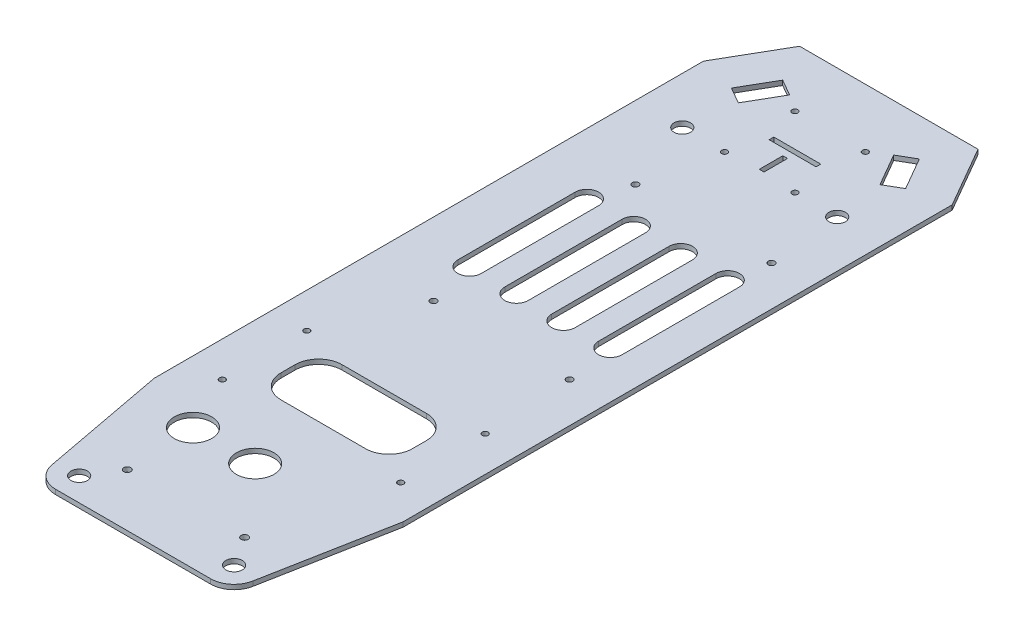
SolidWorks part; units mm, degrees
material "Epoxy, renforcé"
ref_plane "Plan de face" through (0, 0, 0) normal (0, 0, 1) x (1, 0, 0)
ref_plane "Plan de dessus" through (0, 0, 0) normal (0, 1, 0) x (1, 0, 0)
ref_plane "Plan de droite" through (0, 0, 0) normal (1, 0, 0) x (0, 0, -1)
sketch "Esquisse1" plane through (0, 0, 0) normal (0, 1, 0) x (1, 0, 0)
  line L0 (-33, 128.5) -> (33, 128.5) construction
  line L1 (33, 128.5) -> (33, -128.5) construction
  line L2 (33, -128.5) -> (-33, -128.5) construction
  line L3 (-33, -128.5) -> (-33, 128.5) construction
  line L4 (0, 128.5) -> (0, 0) construction
  line L5 (33, 0) -> (0, 0) construction
  line L6 (53, 183.5) -> (-53, 183.5)
  line L7 (-53, 183.5) -> (-53, -148.5)
  line L8 (-53, -148.5) -> (53, -148.5)
  line L9 (53, 183.5) -> (53, -148.5)
  circle A0 centre (-33, 128.5) radius 3.5
  circle A1 centre (-33, -128.5) radius 3.5
  circle A2 centre (33, 128.5) radius 3.5
  circle A3 centre (33, -128.5) radius 3.5
  point P17 (0, -148.5)
  point P18 (0, 183.5)
  dimension "D1" = 7
  dimension "D2" = 7
  dimension "D3" = 7
  dimension "D4" = 7
  dimension "D5" = 66
  dimension "D6" = 257
  dimension "D7" = 55
  dimension "D8" = 20
  dimension "D9" = 20
extrude "Boss.-Extru.1" add sketch "Esquisse1" along normal blind 2
sketch "Esquisse3" plane through (0, 2, 0) normal (0, 1, 0) x (1, 0, 0)
  line L0 (-22, 11.5) -> (-22, 97.5) construction
  line L1 (-22, 97.5) -> (36, 97.5) construction
  line L2 (36, 97.5) -> (36, 11.5) construction
  line L3 (36, 11.5) -> (-22, 11.5) construction
  line L4 (53, -148.5) -> (53, 183.5) construction
  line L5 (53, 183.5) -> (-53, 183.5) construction
  circle A4 centre (-22, 11.5) radius 1.375
  circle A5 centre (-22, 97.5) radius 1.375
  circle A6 centre (36, 97.5) radius 1.375
  circle A7 centre (36, 11.5) radius 1.375
  dimension "D1" = 86
  dimension "D2" = 58
  dimension "D3" = 17
  dimension "D4" = 86
extrude "Enlèv. mat.-Extru.1" cut sketch "Esquisse3" against normal through all
chamfer "Chanfrein1" distance 15 angle 60 2 edges at (-53, 1, -183.5) (53, 1, -183.5) first distance on face at (0, 1, -183.5)
sketch "Esquisse4" plane through (0, 2, 0) normal (0, 1, 0) x (1, 0, 0)
  line L0 (0, -62.5) -> (0, -148.5) construction
  line L1 (38, -62.5) -> (-38, -62.5) construction
  line L2 (38, -62.5) -> (38, -26.5) construction
  line L3 (38, -26.5) -> (-38, -26.5) construction
  line L4 (-38, -62.5) -> (-38, -26.5) construction
  line L5 (-53, -148.5) -> (53, -148.5) construction
  line L6 (38, 183.5) -> (-38, 183.5) construction
  line L7 (-28, -57.5) -> (28, -57.5)
  line L8 (-28, -57.5) -> (-28, -31.5)
  line L9 (-28, -31.5) -> (28, -31.5)
  line L10 (28, -57.5) -> (28, -31.5)
  circle A0 centre (38, -62.5) radius 1.25
  circle A1 centre (38, -26.5) radius 1.25
  circle A2 centre (-38, -62.5) radius 1.25
  circle A3 centre (-38, -26.5) radius 1.25
  dimension "D3" = 2.5
  dimension "D4" = 2.5
  dimension "D5" = 2.5
  dimension "D6" = 2.5
  dimension "D1" = 76
  dimension "D2" = 36
  dimension "D7" = 210
  dimension "D8" = 10
  dimension "D9" = 10
  dimension "D10" = 10
  dimension "D11" = 10
extrude "Enlèv. mat.-Extru.2" cut sketch "Esquisse4" against normal blind 10
fillet "Congé1" radius 10 4 edges at (28, 1, 57.5) (28, 1, 31.5) (-28, 1, 31.5) (-28, 1, 57.5)
sketch "Esquisse5" plane through (0, 2, 0) normal (0, 1, 0) x (1, 0, 0)
  line L1 (-22, 11.5) -> (36, 11.5) construction
  line L2 (-22, 11.5) -> (-22, 97.5) construction
  line L3 (-22, 97.5) -> (36, 97.5) construction
  line L4 (36, 11.5) -> (36, 97.5) construction
  line L5 (-17, 16.5) -> (23.5, 16.5)
  line L6 (-17, 16.5) -> (-17, 92.5)
  line L7 (-17, 92.5) -> (23.5, 92.5)
  line L8 (23.5, 16.5) -> (23.5, 92.5)
  dimension "D1" = 10
  dimension "D2" = 10
  dimension "D3" = 25
  dimension "D4" = 10
extrude "Enlèv. mat.-Extru.3" [suppressed] cut sketch "Esquisse5" against normal blind 10
fillet "Congé2" [suppressed] radius 10
sketch "Esquisse6" plane through (0, 2, 0) normal (0, 1, 0) x (1, 0, 0)
  line L0 (0, 183.5) -> (0, 143.5) construction
  line L2 (38, 183.5) -> (-38, 183.5) construction
  line L3 (15, 128.5) -> (-15, 128.5) construction
  line L4 (15, 128.5) -> (15, 158.5) construction
  line L5 (15, 158.5) -> (-15, 158.5) construction
  line L6 (-15, 128.5) -> (-15, 158.5) construction
  line L7 (15, 128.5) -> (-15, 158.5) construction
  line L8 (15, 158.5) -> (-15, 128.5) construction
  line L9 (-10, 142.5) -> (10, 142.5)
  line L10 (-10, 142.5) -> (-10, 144.5)
  line L11 (-10, 144.5) -> (10, 144.5)
  line L12 (10, 142.5) -> (10, 144.5)
  line L13 (-10, 142.5) -> (10, 144.5) construction
  line L14 (-10, 144.5) -> (10, 142.5) construction
  line L15 (-1.1799, 129.5) -> (0.8201, 129.5)
  line L16 (-1.1799, 129.5) -> (-1.1799, 139.5)
  line L17 (-1.1799, 139.5) -> (0.8201, 139.5)
  line L18 (0.8201, 129.5) -> (0.8201, 139.5)
  line L19 (-1.1799, 129.5) -> (0.8201, 139.5) construction
  line L20 (-1.1799, 139.5) -> (0.8201, 129.5) construction
  circle A0 centre (-15, 128.5) radius 1.25
  circle A1 centre (15, 128.5) radius 1.25
  circle A2 centre (-15, 158.5) radius 1.25
  circle A3 centre (15, 158.5) radius 1.25
  point P16 (-0.1799, 134.5)
  dimension "D4" = 2.5
  dimension "D5" = 2.5
  dimension "D6" = 2.5
  dimension "D7" = 2.5
  dimension "D1" = 30
  dimension "D2" = 30
  dimension "D3" = 40
  dimension "D8" = 20
  dimension "D9" = 2
  dimension "D10" = 10
  dimension "D11" = 2
  dimension "D12" = 3
extrude "Enlèv. mat.-Extru.4" cut sketch "Esquisse6" against normal blind 10
sketch "Esquisse7" plane through (0, 2, 0) normal (0, 1, 0) x (1, 0, 0)
  line L0 (0, -86.5) -> (0, -148.5) construction
  line L1 (-53, -148.5) -> (53, -148.5) construction
  line L2 (0, -86.5) -> (-53, -86.5) construction
  line L3 (-53, 157.5192) -> (-53, -148.5) construction
  line L4 (38, 183.5) -> (-38, 183.5) construction
  circle A0 centre (0, -86.5) radius 8
  circle A1 centre (-26.5, -86.5) radius 8
  dimension "D1" = 16
  dimension "D3" = 16
  dimension "D2" = 270
extrude "Enlèv. mat.-Extru.5" cut sketch "Esquisse7" against normal blind 10
sketch "Esquisse8" plane through (0, 2, 0) normal (0, 1, 0) x (1, 0, 0)
  line L0 (38, 183.5) -> (-38, 183.5)
  line L1 (38, 183.5) -> (-38, 183.5) construction
  line L2 (-38, 183.5) -> (-53, 157.5192)
  line L3 (-53, 157.5192) -> (-53, -76.5)
  line L4 (-53, 157.5192) -> (-53, -148.5) construction
  line L5 (-53, -76.5) -> (-42.8262, -130.3562)
  line L6 (-33, -138.5) -> (33, -138.5)
  line L7 (0, -148.5) -> (0, 183.5) construction
  line L8 (-53, -148.5) -> (53, -148.5) construction
  line L9 (53, -76.5) -> (42.8262, -130.3562)
  line L10 (53, 157.5192) -> (53, -76.5)
  line L11 (38, 183.5) -> (53, 157.5192)
  arc A0 (-42.8262, -130.3562) -> (-33, -138.5) centre (-33, -128.5) ccw
  arc A1 (42.8262, -130.3562) -> (33, -138.5) centre (33, -128.5) cw
  point P22 (0, -138.5)
  dimension "D1" = 20
  dimension "D2" = 260
extrude "Enlèv. mat.-Extru.6" cut sketch "Esquisse8" against normal blind 10 flip side to cut
sketch "Esquisse9" plane through (0, 2, 0) normal (0, 1, 0) x (1, 0, 0)
  line L0 (53, 10.4239) -> (-53, 10.4239) construction
  line L1 (53, -76.5) -> (53, 157.5192) construction
  line L2 (-53, 157.5192) -> (-53, -76.5) construction
  circle A0 centre (45, 10.4239) radius 3.5
  circle A1 centre (-45, 10.4239) radius 3.5
  dimension "D1" = 7
  dimension "D3" = 7
  dimension "D2" = 8
  dimension "D4" = 8
extrude "Enlèv. mat.-Extru.7" [suppressed] cut sketch "Esquisse9" against normal blind 10
sketch "Esquisse10" plane through (0, 0, 0) normal (0, -1, 0) x (1, 0, 0)
  line L0 (38, -183.5) -> (53, -157.5192) construction
  line L1 (55.5, -153.1891) -> (37.3135, -142.6891) construction
  line L2 (55.5, -153.1891) -> (38, -183.5) construction
  line L3 (38, -183.5) -> (19.8135, -173) construction
  line L4 (37.3135, -142.6891) -> (19.8135, -173) construction
  line L5 (55.5, -153.1891) -> (19.8135, -173) construction
  line L6 (38, -183.5) -> (37.3135, -142.6891) construction
  line L7 (28.5635, -157.8446) -> (37.6567, -163.0946) construction
  line L8 (32.5635, -150.9164) -> (30.1819, -149.5414)
  line L9 (30.1819, -149.5414) -> (26.1868, -156.461)
  line L10 (32.5635, -150.9164) -> (37.1101, -153.5414)
  line L11 (37.1101, -153.5414) -> (29.1101, -167.3978)
  line L12 (24.5635, -164.7728) -> (29.1101, -167.3978)
  line L13 (22.1819, -163.3978) -> (26.1868, -156.461)
  line L14 (24.5635, -164.7728) -> (22.1819, -163.3978)
  line L15 (0, -183.5) -> (0, -146.2698) construction
  line L18 (38, -183.5) -> (-38, -183.5) construction
  line L19 (-28.5635, -157.8446) -> (-37.6567, -163.0946) construction
  line L20 (-38, -183.5) -> (-37.3135, -142.6891) construction
  line L21 (-55.5, -153.1891) -> (-19.8135, -173) construction
  line L22 (-37.3135, -142.6891) -> (-19.8135, -173) construction
  line L23 (-38, -183.5) -> (-19.8135, -173) construction
  line L24 (-55.5, -153.1891) -> (-38, -183.5) construction
  line L25 (-55.5, -153.1891) -> (-37.3135, -142.6891) construction
  line L26 (-24.5635, -164.7728) -> (-22.1819, -163.3978)
  line L27 (-22.1819, -163.3978) -> (-26.1868, -156.461)
  line L28 (-24.5635, -164.7728) -> (-29.1101, -167.3978)
  line L29 (-37.1101, -153.5414) -> (-29.1101, -167.3978)
  line L30 (-32.5635, -150.9164) -> (-37.1101, -153.5414)
  line L31 (-30.1819, -149.5414) -> (-26.1868, -156.461)
  line L32 (-32.5635, -150.9164) -> (-30.1819, -149.5414)
  point P0 (37.6567, -163.0946)
  point P16 (33.1101, -160.4696)
  point P38 (-33.1101, -160.4696)
  point P39 (26.5799, -155.7801)
  point P40 (26.164, -156.4386)
  dimension "D3" = 8
  dimension "D1" = 21
  dimension "D2" = 35
  dimension "D4" = 8
extrude "Enlèv. mat.-Extru.8" cut sketch "Esquisse10" against normal blind 10
sketch "Esquisse11" plane through (0, 0, 0) normal (0, -1, 0) x (1, 0, 0)
  line L0 (25, 116) -> (0, 116) construction
  line L1 (17.5, 126.5) -> (-17.5, 126.5) construction
  line L2 (17.5, 126.5) -> (17.5, 105.5) construction
  line L3 (17.5, 105.5) -> (-17.5, 105.5) construction
  line L4 (-17.5, 126.5) -> (-17.5, 105.5) construction
  line L5 (17.5, 126.5) -> (-17.5, 105.5) construction
  line L6 (17.5, 105.5) -> (-17.5, 126.5) construction
  line L7 (0, 116) -> (0, 105.5) construction
  line L8 (0, 138.5) -> (0, 126.5) construction
  line L9 (-33, 138.5) -> (33, 138.5) construction
  circle A0 centre (25, 116) radius 1.5
  circle A1 centre (-25, 116) radius 1.5
  point P0 (0, 116)
  dimension "D3" = 3
  dimension "D1" = 21
  dimension "D2" = 35
  dimension "D4" = 25
  dimension "D5" = 12
extrude "Enlèv. mat.-Extru.9" cut sketch "Esquisse11" against normal blind 10
sketch "Esquisse12" plane through (0, 0, 0) normal (0, -1, 0) x (1, 0, 0)
  line L0 (33, -31.8433) -> (33, -81.8433) construction
  line L1 (38, -31.8433) -> (38, -81.8433)
  line L2 (28, -31.8433) -> (28, -81.8433)
  line L3 (13, -31.8433) -> (13, -81.8433) construction
  line L4 (18, -31.8433) -> (18, -81.8433)
  line L5 (8, -31.8433) -> (8, -81.8433)
  line L6 (-7, -31.8433) -> (-7, -81.8433) construction
  line L7 (-2, -31.8433) -> (-2, -81.8433)
  line L8 (-12, -31.8433) -> (-12, -81.8433)
  line L9 (-27, -31.8433) -> (-27, -81.8433) construction
  line L10 (-22, -31.8433) -> (-22, -81.8433)
  line L11 (-32, -31.8433) -> (-32, -81.8433)
  line L12 (53, 76.5) -> (53, -157.5192) construction
  arc A0 (38, -31.8433) -> (28, -31.8433) centre (33, -31.8433) ccw
  arc A1 (28, -81.8433) -> (38, -81.8433) centre (33, -81.8433) ccw
  arc A2 (18, -31.8433) -> (8, -31.8433) centre (13, -31.8433) ccw
  arc A3 (8, -81.8433) -> (18, -81.8433) centre (13, -81.8433) ccw
  arc A4 (-2, -31.8433) -> (-12, -31.8433) centre (-7, -31.8433) ccw
  arc A5 (-12, -81.8433) -> (-2, -81.8433) centre (-7, -81.8433) ccw
  arc A6 (-22, -31.8433) -> (-32, -31.8433) centre (-27, -31.8433) ccw
  arc A7 (-32, -81.8433) -> (-22, -81.8433) centre (-27, -81.8433) ccw
  point P2 (33, -56.8433)
  point P10 (13, -56.8433)
  point P17 (-7, -56.8433)
  point P24 (-27, -56.8433)
  dimension "D1" = 10
  dimension "D2" = 50
  dimension "D4" = 20
  dimension "D3" = 4
extrude "Enlèv. mat.-Extru.10" cut sketch "Esquisse12" against normal blind 10
